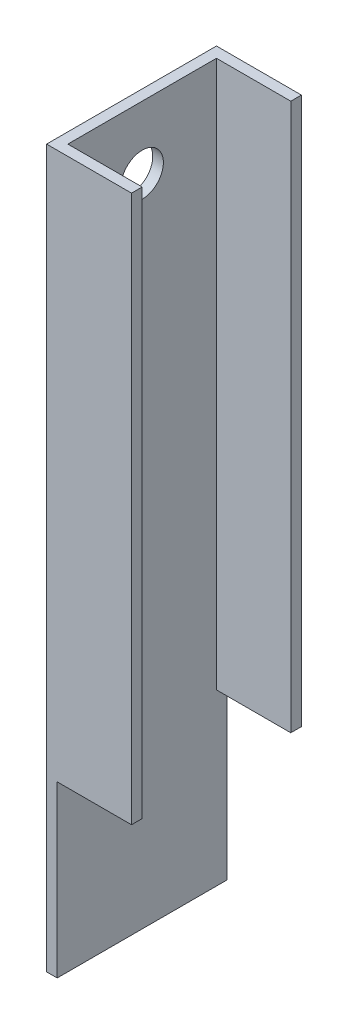
SolidWorks part; units mm, degrees
ref_plane "Front Plane" through (0, 0, 0) normal (0, 0, 1) x (1, 0, 0)
ref_plane "Top Plane" through (0, 0, 0) normal (0, 1, 0) x (1, 0, 0)
ref_plane "Right Plane" through (0, 0, 0) normal (1, 0, 0) x (0, 0, -1)
sketch "Sketch1" plane through (0, 0, 0) normal (0, 1, 0) x (1, 0, 0)
  line L0 (-20.955, 0) -> (-20.955, 25.4)
  line L1 (-20.955, 25.4) -> (4.445, 25.4)
  line L2 (4.445, 25.4) -> (4.445, 22.225)
  line L3 (4.445, 22.225) -> (-17.78, 22.225)
  line L4 (-17.78, 22.225) -> (-17.78, -22.225)
  line L5 (-17.78, -22.225) -> (4.445, -22.225)
  line L6 (4.445, -22.225) -> (4.445, -25.4)
  line L7 (4.445, -25.4) -> (-20.955, -25.4)
  line L8 (-20.955, -25.4) -> (-20.955, 0)
  dimension "D1" = 3.175
  dimension "D2" = 3.175
  dimension "D3" = 3.175
  dimension "D4" = 25.4
  dimension "D5" = 25.4
  dimension "D6" = 25.4
  dimension "D7" = 25.4
extrude "Boss-Extrude1" add sketch "Sketch1" along normal mid plane 214.376
sketch "Sketch2" plane through (0, 0, 25.4) normal (0, 0, 1) x (1, 0, 0)
  line L0 (-17.78, -107.188) -> (-17.78, -56.388)
  line L1 (-20.955, -107.188) -> (4.445, -107.188) construction
  line L2 (-17.78, -56.388) -> (4.445, -56.388)
  line L3 (4.445, 107.188) -> (4.445, -107.188) construction
  line L4 (4.445, -56.388) -> (4.445, -107.188)
  line L5 (4.445, -107.188) -> (-17.78, -107.188)
  line L6 (-20.955, 107.188) -> (-20.955, -107.188) construction
  dimension "D1" = 3.175
  dimension "D2" = 22.225
  dimension "D3" = 50.8
extrude "Cut-Extrude1" cut sketch "Sketch2" against normal blind 208.026
sketch "Sketch3" plane through (-20.955, 0, 0) normal (-1, 0, 0) x (0, 0, 1)
  line L1 (-25.4, -107.188) -> (25.4, -107.188) construction
  circle A0 centre (0, 88.138) radius 6.35
  dimension "D1" = 12.7
  dimension "D2" = 195.326
extrude "Cut-Extrude2" cut sketch "Sketch3" against normal blind 45.974
